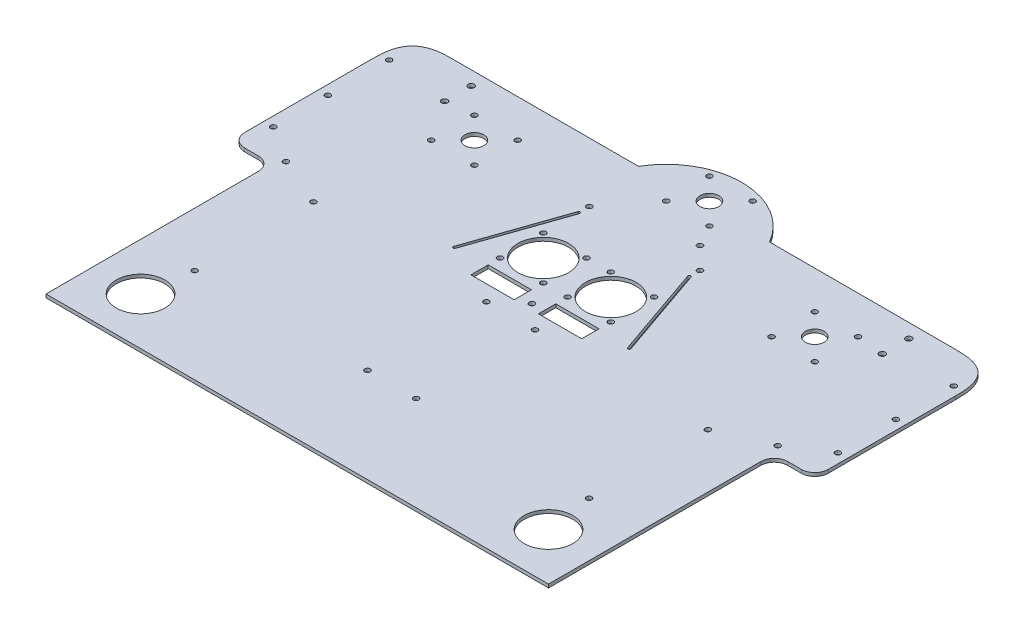
SolidWorks part; units mm, degrees
ref_plane "Front Plane" through (0, 0, 0) normal (0, 0, 1) x (1, 0, 0)
ref_plane "Top Plane" through (0, 0, 0) normal (0, 1, 0) x (1, 0, 0)
ref_plane "Right Plane" through (0, 0, 0) normal (1, 0, 0) x (0, 0, -1)
sketch "Sketch1" plane through (0, 0, 0) normal (0, 1, 0) x (1, 0, 0)
  line L1 (-103.134, 171.9149) -> (328.866, 171.9149)
  line L2 (-103.134, 171.9149) -> (-103.134, -28.0851)
  line L3 (-103.134, -28.0851) -> (328.866, -28.0851)
  line L4 (328.866, 171.9149) -> (328.866, -28.0851)
extrude "Boss-Extrude1" add sketch "Sketch1" along normal blind 2.5 contours L1 L4 L3 L2
sketch "Sketch3" plane through (0, 2.5, 0) normal (0, 1, 0) x (1, 0, 0)
  line L0 (-13.134, 71.9149) -> (-29.1359, 55.9131)
  line L1 (2.8678, 87.9167) -> (-29.1359, 87.9167)
  line L2 (2.8678, 87.9167) -> (2.8678, 55.9131)
  line L3 (2.8678, 55.9131) -> (-29.1359, 55.9131)
  line L4 (-29.1359, 87.9167) -> (-29.1359, 55.9131)
  line L5 (2.8678, 87.9167) -> (-29.1359, 55.9131) construction
  line L6 (2.8678, 55.9131) -> (-29.1359, 87.9167) construction
  line L7 (-103.134, 71.9149) -> (-13.134, 71.9149)
  line L8 (-103.134, 171.9149) -> (-103.134, -28.0851) construction
  line L9 (238.866, 71.9149) -> (238.866, 115.9149)
  line L14 (62.253, -0.3819) -> (46.2512, -16.3837)
  line L15 (238.866, 115.9149) -> (328.866, 115.9149)
  line L18 (328.866, 171.9149) -> (328.866, -28.0851) construction
  line L19 (238.866, 71.9149) -> (222.8641, 55.9131)
  line L20 (254.8678, 87.9167) -> (222.8641, 87.9167)
  line L21 (254.8678, 87.9167) -> (254.8678, 55.9131)
  line L22 (254.8678, 55.9131) -> (222.8641, 55.9131)
  line L23 (222.8641, 87.9167) -> (222.8641, 55.9131)
  line L24 (254.8678, 87.9167) -> (222.8641, 55.9131) construction
  line L25 (254.8678, 55.9131) -> (222.8641, 87.9167) construction
  line L27 (328.866, 71.9149) -> (238.866, 71.9149)
  line L28 (238.866, 115.9149) -> (238.866, 171.9149)
  line L29 (238.866, 171.9149) -> (328.866, 171.9149)
  line L30 (328.866, 115.9149) -> (328.866, 171.9149)
  line L31 (328.866, 115.9149) -> (-169.3435, 115.9149)
  line L32 (328.866, 115.9149) -> (328.866, 173.2785)
  line L33 (328.866, 173.2785) -> (-169.3435, 173.2785)
  line L34 (-169.3435, 115.9149) -> (-169.3435, 173.2785)
  line L35 (78.2549, 15.6199) -> (46.2512, 15.6199)
  line L36 (78.2549, 15.6199) -> (78.2549, -16.3837)
  line L37 (78.2549, -16.3837) -> (46.2512, -16.3837)
  line L38 (46.2512, 15.6199) -> (46.2512, -16.3837)
  line L39 (78.2549, 15.6199) -> (46.2512, -16.3837) construction
  line L40 (78.2549, -16.3837) -> (46.2512, 15.6199) construction
  circle A0 centre (-13.134, 71.9149) radius 7
  circle A1 centre (-29.1359, 55.9131) radius 2
  circle A2 centre (-29.1359, 87.9167) radius 2
  circle A3 centre (2.8678, 87.9167) radius 2
  circle A4 centre (2.8678, 55.9131) radius 2
  circle A10 centre (238.866, 71.9149) radius 7
  circle A11 centre (222.8641, 55.9131) radius 2
  circle A12 centre (222.8641, 87.9167) radius 2
  circle A13 centre (254.8678, 87.9167) radius 2
  circle A14 centre (254.8678, 55.9131) radius 2
  circle A15 centre (62.253, -0.3819) radius 7
  circle A16 centre (46.2512, -16.3837) radius 2
  circle A17 centre (46.2512, 15.6199) radius 2
  circle A18 centre (78.2549, 15.6199) radius 2
  circle A19 centre (78.2549, -16.3837) radius 2
  point P10 (328.866, 71.9149)
extrude "Cut-Extrude1" cut sketch "Sketch3" against normal blind 2.5 contours A2 | A3 | A4 | A1 | A0 | A11 | A14 | A13 | A10 | A12 | L32 L31 L34 L33
sketch "Sketch5" plane through (0, 2.5, 0) normal (0, 1, 0) x (1, 0, 0)
  line L0 (263.7413, -28.0851) -> (263.7413, -18.0851)
  line L3 (-103.134, -28.0851) -> (328.866, -28.0851) construction
  line L5 (263.7413, -18.0851) -> (328.866, -18.0851)
  line L6 (263.7413, -18.0851) -> (263.7413, -28.0851)
  line L7 (263.7413, -28.0851) -> (328.866, -28.0851)
  line L8 (328.866, -18.0851) -> (328.866, -28.0851)
  line L9 (263.7413, -18.0851) -> (-103.134, -18.0851)
  line L10 (263.7413, -18.0851) -> (263.7413, -28.0851)
  line L11 (263.7413, -28.0851) -> (-103.134, -28.0851)
  line L12 (-103.134, -18.0851) -> (-103.134, -28.0851)
  line M12 (328.866, -28.0851) -> (328.866, 115.9149)
  line M14 (-103.134, 115.9149) -> (-103.134, -28.0851)
  line M15 (-103.134, -28.0851) -> (328.866, -28.0851)
extrude "Cut-Extrude3" cut sketch "Sketch5" against normal blind 2.5 contours L0 L9 M14 M15 | L5 L0 M15 M12 region at (80.3036, 2.5, 23.0851) region at (296.3036, 2.5, 23.0851)
sketch "Sketch6" plane through (0, 2.5, 0) normal (0, 1, 0) x (1, 0, 0)
  line L0 (328.866, -18.0851) -> (-103.134, -18.0851) construction
  line L1 (112.866, -18.0851) -> (112.866, 21.9149)
  line L2 (112.866, 21.9149) -> (137.866, 21.9149)
  line L3 (112.866, 21.9149) -> (87.866, 21.9149)
  line L4 (87.866, 21.9149) -> (71.8641, 5.9131)
  line L5 (103.8678, 37.9167) -> (71.8641, 37.9167)
  line L6 (103.8678, 37.9167) -> (103.8678, 5.9131)
  line L7 (103.8678, 5.9131) -> (71.8641, 5.9131)
  line L8 (71.8641, 37.9167) -> (71.8641, 5.9131)
  line L9 (103.8678, 37.9167) -> (71.8641, 5.9131) construction
  line L10 (103.8678, 5.9131) -> (71.8641, 37.9167) construction
  line L11 (137.866, 21.9149) -> (121.8641, 5.9131)
  line L12 (153.8678, 37.9167) -> (121.8641, 37.9167)
  line L13 (153.8678, 37.9167) -> (153.8678, 5.9131)
  line L14 (153.8678, 5.9131) -> (121.8641, 5.9131)
  line L15 (121.8641, 37.9167) -> (121.8641, 5.9131)
  line L16 (153.8678, 37.9167) -> (121.8641, 5.9131) construction
  line L17 (153.8678, 5.9131) -> (121.8641, 37.9167) construction
  circle A0 centre (137.866, 21.9149) radius 18.75
  circle A1 centre (87.866, 21.9149) radius 18.75
  circle A2 centre (87.866, 21.9149) radius 7
  circle A3 centre (71.8641, 5.9131) radius 2
  circle A4 centre (71.8641, 37.9167) radius 2
  circle A5 centre (103.8678, 37.9167) radius 2
  circle A6 centre (103.8678, 5.9131) radius 2
  circle A7 centre (137.866, 21.9149) radius 7
  circle A8 centre (121.8641, 5.9131) radius 2
  circle A9 centre (121.8641, 37.9167) radius 2
  circle A10 centre (153.8678, 37.9167) radius 2
  circle A11 centre (153.8678, 5.9131) radius 2
  point P0 (112.866, -18.0851)
extrude "Cut-Extrude4" cut sketch "Sketch6" against normal blind 2.5 contours A11 | A8 | A10 | A9 | A5 | A6 | A3 | A4
sketch "Sketch8" plane through (0, 2.5, 0) normal (0, 1, 0) x (1, 0, 0)
  line L2 (153.8678, 5.9131) -> (153.8678, 90.0973)
  line L3 (153.8678, 90.0973) -> (71.8641, 90.0973)
  line L4 (71.8641, 90.0973) -> (71.8641, 5.9131)
  line L5 (153.8678, 64.0929) -> (71.8641, 64.0929)
  line L10 (177.527, -4.0851) -> (153.8678, 64.0929) construction
  line L14 (176.5823, -4.4129) -> (152.9231, 63.7651)
  line L15 (178.4718, -3.7572) -> (154.8125, 64.4208)
  line L16 (48.2049, -4.0851) -> (71.8641, 64.0929) construction
  line L17 (47.2602, -3.7572) -> (70.9194, 64.4208)
  line L18 (49.1496, -4.4129) -> (72.8089, 63.7651)
  arc A6 (176.5823, -4.4129) -> (178.4718, -3.7572) centre (177.527, -4.0851) ccw
  arc A7 (154.8125, 64.4208) -> (152.9231, 63.7651) centre (153.8678, 64.0929) ccw
  arc A8 (47.2602, -3.7572) -> (49.1496, -4.4129) centre (48.2049, -4.0851) ccw
  arc A9 (72.8089, 63.7651) -> (70.9194, 64.4208) centre (71.8641, 64.0929) ccw
  point P17 (177.527, 5.9131)
  point P18 (48.2049, 5.9131)
  point P19 (165.6974, 30.0039)
  point P22 (112.866, -4.0851)
  point P27 (60.0345, 30.0039)
extrude "Cut-Extrude5" cut sketch "Sketch8" against normal blind 2.5 contours L17 A9 L18 A8 | L15 A7 L14 A6
fillet "Fillet1" radius 30 2 edges at (-103.134, 1.25, -115.9149) (328.866, 1.25, -115.9149) curvature continuous yes
sketch "Sketch9" plane through (0, 2.5, 0) normal (0, 1, 0) x (1, 0, 0)
  line L0 (328.866, 62.6221) -> (321.866, 62.6221)
  line L1 (328.866, 85.9149) -> (328.866, -18.0851) construction
  line L2 (321.866, 109.7214) -> (321.866, -11.8915)
  line L3 (321.866, 6.0103) -> (321.866, -11.8915)
  line L4 (321.866, 109.7214) -> (321.866, 91.8196)
  line L5 (321.866, 91.8196) -> (321.866, 109.7214)
  line L6 (-103.134, 46.4673) -> (-96.134, 46.4673)
  line L7 (-103.134, 85.9149) -> (-103.134, -18.0851) construction
  line L8 (-96.134, 46.4673) -> (-96.134, 109.7214)
  line L9 (-96.134, 109.7214) -> (-96.134, -11.8916)
  line L10 (-96.134, -11.8916) -> (-96.134, 6.0103)
  line L11 (-96.134, 109.7214) -> (-96.134, 97.3154)
  line L12 (-96.134, 109.7214) -> (-96.134, 91.8196)
  circle A0 centre (321.866, 6.0103) radius 2
  circle A1 centre (321.866, 48.9149) radius 2
  circle A2 centre (321.866, 91.8196) radius 2
  circle A3 centre (-96.134, 46.4673) radius 2
  circle A4 centre (-96.134, 91.8196) radius 2
  circle A5 centre (-96.134, 6.0103) radius 2
  spline S0 degree 2 poles (328.866, 85.9149) (328.866, 87.9765) (328.8467, 89.0459) (328.8162, 90.7467) (328.7231, 92.1742) (328.5043, 95.5283) (327.8783, 98.3317) (326.3274, 105.2776) (322.2688, 109.3319) (318.2198, 113.3765) (311.2895, 114.9258) (308.4764, 115.5546) (305.1048, 115.7733) (303.6844, 115.8655) (301.9893, 115.8958) (300.9233, 115.9149) (298.866, 115.9149) knots 0 0 0 0.0625 0.0625 0.125 0.125 0.25 0.25 0.5 0.5 0.75 0.75 0.875 0.875 0.9375 0.9375 1 1 1 construction
  spline S1 degree 2 poles (298.866, -18.0851) (300.9275, -18.0851) (301.997, -18.0659) (303.6978, -18.0353) (305.1253, -17.9422) (308.4794, -17.7234) (311.2827, -17.0975) (318.2287, -15.5466) (322.283, -11.4879) (326.3276, -7.4389) (327.8768, -0.5086) (328.5057, 2.3045) (328.7244, 5.6761) (328.8165, 7.0965) (328.8469, 8.7916) (328.866, 9.8575) (328.866, 11.9149) knots 0 0 0 0.0625 0.0625 0.125 0.125 0.25 0.25 0.5 0.5 0.75 0.75 0.875 0.875 0.9375 0.9375 1 1 1 construction
  spline S2 degree 2 poles (-73.134, 115.9149) (-75.1956, 115.9149) (-76.2651, 115.8957) (-77.9658, 115.8651) (-79.3933, 115.772) (-82.7474, 115.5532) (-85.5508, 114.9273) (-92.4967, 113.3764) (-96.551, 109.3177) (-100.5957, 105.2687) (-102.1449, 98.3384) (-102.7737, 95.5254) (-102.9924, 92.1538) (-103.0846, 90.7333) (-103.1149, 89.0383) (-103.134, 87.9723) (-103.134, 85.9149) knots 0 0 0 0.0625 0.0625 0.125 0.125 0.25 0.25 0.5 0.5 0.75 0.75 0.875 0.875 0.9375 0.9375 1 1 1 construction
  spline S3 degree 2 poles (-103.134, 11.9149) (-103.134, 9.8534) (-103.1148, 8.7839) (-103.0842, 7.0831) (-102.9911, 5.6556) (-102.7723, 2.3015) (-102.1464, -0.5019) (-100.5955, -7.4478) (-96.5368, -11.5021) (-92.4879, -15.5467) (-85.5575, -17.0959) (-82.7445, -17.7248) (-79.3729, -17.9435) (-77.9525, -18.0356) (-76.2574, -18.066) (-75.1914, -18.0851) (-73.134, -18.0851) knots 0 0 0 0.0625 0.0625 0.125 0.125 0.25 0.25 0.5 0.5 0.75 0.75 0.875 0.875 0.9375 0.9375 1 1 1 construction
extrude "Cut-Extrude6" cut sketch "Sketch9" against normal blind 2.5 contours A0 | A1 | A2 | A5 | A3 | A4
sketch "Sketch10" plane through (0, 2.5, 0) normal (0, 1, 0) x (1, 0, 0)
  line L0 (232.1904, -18.0851) -> (232.1904, -11.5851)
  line L1 (328.866, -18.0851) -> (-103.134, -18.0851) construction
  line L2 (322.1851, -11.5851) -> (-96.4532, -11.5851)
  line L3 (322.1851, -11.5851) -> (232.1904, -11.5851)
  line L4 (322.1851, -11.5851) -> (232.1904, -11.5851)
  line L5 (322.1851, -11.5851) -> (232.1904, -11.5851)
  line L6 (322.1851, -11.5851) -> (294.9418, -11.5851)
  line L7 (-96.4532, -11.5851) -> (-78.7572, -11.5851)
  line L8 (-96.4532, -11.5851) -> (-69.2097, -11.5851)
  circle A0 centre (112.866, -11.5851) radius 2
  circle A3 centre (294.9418, -11.5851) radius 2
  circle A4 centre (-69.2097, -11.5851) radius 2
  spline S0 degree 2 poles (298.866, -18.0851) (300.9275, -18.0851) (301.997, -18.0659) (303.6978, -18.0353) (305.1253, -17.9422) (308.4794, -17.7234) (311.2827, -17.0975) (318.2287, -15.5466) (322.283, -11.4879) (326.3276, -7.4389) (327.8768, -0.5086) (328.5057, 2.3045) (328.7244, 5.6761) (328.8165, 7.0965) (328.8469, 8.7916) (328.866, 9.8575) (328.866, 11.9149) knots 0 0 0 0.0625 0.0625 0.125 0.125 0.25 0.25 0.5 0.5 0.75 0.75 0.875 0.875 0.9375 0.9375 1 1 1 construction
  spline S1 degree 2 poles (-103.134, 11.9149) (-103.134, 9.8534) (-103.1148, 8.7839) (-103.0842, 7.0831) (-102.9911, 5.6556) (-102.7723, 2.3015) (-102.1464, -0.5019) (-100.5955, -7.4478) (-96.5368, -11.5021) (-92.4879, -15.5467) (-85.5575, -17.0959) (-82.7445, -17.7248) (-79.3729, -17.9435) (-77.9525, -18.0356) (-76.2574, -18.066) (-75.1914, -18.0851) (-73.134, -18.0851) knots 0 0 0 0.0625 0.0625 0.125 0.125 0.25 0.25 0.5 0.5 0.75 0.75 0.875 0.875 0.9375 0.9375 1 1 1 construction
extrude "Cut-Extrude7" cut sketch "Sketch10" against normal blind 2.5 contours A4 | A0 | A3
extrude "Cut-Extrude8" cut sketch "Sketch6<3>" against normal blind 10 contours A1 | A0
sketch "Sketch6<3>" plane through (0, 2.5, 0) normal (0, 1, 0) x (1, 0, 0) same geometry as "Sketch6"
sketch "Sketch12" plane through (0, 2.5, 0) normal (0, 1, 0) x (1, 0, 0)
  line L0 (121.8641, 37.9167) -> (121.8641, 71.9149)
  line L1 (238.866, 71.9149) -> (-13.134, 71.9149)
  line L3 (121.8641, 71.9149) -> (105.8623, 55.9131)
  line L4 (137.866, 87.9167) -> (105.8623, 87.9167)
  line L5 (137.866, 87.9167) -> (137.866, 55.9131)
  line L6 (137.866, 55.9131) -> (105.8623, 55.9131)
  line L7 (105.8623, 87.9167) -> (105.8623, 55.9131)
  line L8 (137.866, 87.9167) -> (105.8623, 55.9131) construction
  line L9 (137.866, 55.9131) -> (105.8623, 87.9167) construction
  circle A1 centre (121.8641, 71.9149) radius 7
  circle A2 centre (105.8623, 55.9131) radius 2
  circle A3 centre (105.8623, 87.9167) radius 2
  circle A4 centre (137.866, 87.9167) radius 2
  circle A5 centre (137.866, 55.9131) radius 2
extrude "Cut-Extrude9" cut sketch "Sketch12" against normal blind 10 contours A4
sketch "Sketch13" plane through (0, 2.5, 0) normal (0, 1, 0) x (1, 0, 0)
  line L0 (328.866, 85.9149) -> (274.866, 85.9149)
  line L1 (274.866, 85.9149) -> (274.866, 105.5149)
  line L2 (-103.134, 85.9149) -> (-49.134, 85.9149)
  line L3 (-49.134, 85.9149) -> (-49.134, 105.5149)
  circle A0 centre (274.866, 85.9149) radius 2.25
  circle A1 centre (274.866, 105.5149) radius 2.25
  circle A2 centre (-49.134, 85.9149) radius 2.25
  circle A3 centre (-49.134, 105.5149) radius 2.25
extrude "Cut-Extrude10" cut sketch "Sketch13" against normal blind 10 contours A0 | A1 | A2 | A3
sketch "Sketch14" plane through (0, 2.5, 0) normal (0, 1, 0) x (1, 0, 0)
  line L0 (153.8678, 37.9167) -> (121.8641, 71.9149)
  line L1 (121.8641, 71.9149) -> (153.8678, 71.9149)
  line L2 (71.8641, 37.9167) -> (71.8641, 71.9149)
  circle A0 centre (153.8678, 71.9149) radius 2
  circle A1 centre (71.8641, 71.9149) radius 2
extrude "Cut-Extrude12" cut sketch "Sketch14" against normal blind 2.5 contours A0 | A1
sketch "Sketch19" plane through (0, 2.5, 0) normal (0, 1, 0) x (1, 0, 0)
  line L0 (-73.134, -18.0851) -> (298.866, -18.0851)
  line L1 (-73.134, -18.0851) -> (-73.134, -185.2034)
  line L2 (298.866, -18.0851) -> (298.866, -185.2034)
  line L3 (-73.134, -185.2034) -> (298.866, -185.2034)
extrude "Boss-Extrude5" add sketch "Sketch19" against normal blind 2.5
fillet "Fillet3" radius 10 4 edges at (-103.134, 1.25, 18.0851) (-73.134, 1.25, 18.0851) (328.866, 1.25, 18.0851) (298.866, 1.25, 18.0851)
sketch "Sketch21" plane through (0, 2.5, 0) normal (0, 1, 0) x (1, 0, 0)
  line L1 (298.866, -185.2034) -> (258.866, -185.2034)
  line L2 (298.866, -185.2034) -> (298.866, -115.2034)
  line L3 (298.866, -115.2034) -> (258.866, -115.2034)
  line L4 (258.866, -185.2034) -> (258.866, -115.2034)
  line L5 (258.866, -115.2034) -> (130.866, -115.2034)
  line L6 (258.866, -115.2034) -> (258.866, -27.2034)
  line L7 (258.866, -27.2034) -> (130.866, -27.2034)
  line L8 (130.866, -115.2034) -> (130.866, -27.2034)
  line L9 (-73.134, -185.2034) -> (-33.134, -185.2034)
  line L10 (-73.134, -185.2034) -> (-73.134, -115.2034)
  line L11 (-73.134, -115.2034) -> (-33.134, -115.2034)
  line L12 (-33.134, -185.2034) -> (-33.134, -115.2034)
  line L13 (-33.134, -115.2034) -> (94.866, -115.2034)
  line L14 (-33.134, -115.2034) -> (-33.134, -27.2034)
  line L15 (-33.134, -27.2034) -> (94.866, -27.2034)
  line L16 (94.866, -115.2034) -> (94.866, -27.2034)
  circle A0 centre (258.866, -115.2034) radius 2
  circle A1 centre (130.866, -115.2034) radius 2
  circle A2 centre (94.866, -115.2034) radius 2
  circle A3 centre (-33.134, -115.2034) radius 2
  circle A4 centre (-33.134, -27.2034) radius 2
  circle A5 centre (94.866, -27.2034) radius 2
  circle A6 centre (258.866, -27.2034) radius 2
  circle A7 centre (130.866, -27.2034) radius 2
extrude "Cut-Extrude14" cut sketch "Sketch21" against normal blind 2.5 contours A0 | A6 | A7 | A5 | A1 | A2 | A4 | A3
sketch "Sketch22" plane through (0, 2.5, 0) normal (0, 1, 0) x (1, 0, 0)
  line L0 (121.8641, 5.9131) -> (121.8641, -11.5851)
  line L1 (153.8678, 5.9131) -> (153.8678, -11.5851)
  line L2 (103.8678, 5.9131) -> (103.8678, -20.5636)
  line L3 (153.8678, -2.836) -> (121.8641, -2.836)
  line L4 (153.8678, -2.836) -> (153.8678, -20.5636)
  line L5 (153.8678, -20.5636) -> (121.8641, -20.5636)
  line L6 (121.8641, -2.836) -> (121.8641, -20.5636)
  line L7 (71.8641, 5.9131) -> (71.8641, -20.5636)
  line L8 (121.8641, -20.5636) -> (121.8641, -15.0679)
  line L9 (103.8678, -20.5636) -> (71.8641, -20.5636)
  line L10 (103.8678, -20.5636) -> (103.8678, -2.836)
  line L11 (103.8678, -2.836) -> (71.8641, -2.836)
  line L12 (71.8641, -20.5636) -> (71.8641, -2.836)
  line L13 (121.8641, -20.5636) -> (121.8641, -18.0057)
  line L14 (153.8678, -20.5636) -> (153.8678, -16.8822)
  line L15 (153.8678, -20.5636) -> (153.8678, -15.6536)
  line L16 (153.8678, -15.6536) -> (121.8641, -15.6536)
  line L17 (121.8641, -15.6536) -> (103.8678, -15.6536)
  line L18 (103.8678, -15.6536) -> (71.8641, -15.6536)
extrude "Cut-Extrude15" cut sketch "Sketch22" against normal blind 10 contours L0 L6 L5 L4 L1 L3 | L2 L11 L7 L9 region at (137.866, 2.5, 9.2448) region at (87.866, 2.5, 9.2448)
sketch "Sketch23" plane through (0, 2.5, 0) normal (0, 1, 0) x (1, 0, 0)
  line L1 (-73.134, -185.2034) -> (-38.134, -185.2034)
  line L2 (-73.134, -185.2034) -> (-73.134, -150.2034)
  line L3 (-73.134, -150.2034) -> (-38.134, -150.2034)
  line L4 (-38.134, -185.2034) -> (-38.134, -150.2034)
  circle A0 centre (-38.134, -150.2034) radius 18
extrude "Cut-Extrude16" cut sketch "Sketch23" against normal blind 26 contours L4 A0 L3 | L3 A0 L4 region at (-45.7735, 2.5, 157.8428) region at (-35.5876, 2.5, 147.6569)
sketch "Sketch24" plane through (0, 2.5, 0) normal (0, 1, 0) x (1, 0, 0)
  line L1 (298.866, -185.2034) -> (263.866, -185.2034)
  line L2 (298.866, -185.2034) -> (298.866, -150.2034)
  line L3 (298.866, -150.2034) -> (263.866, -150.2034)
  line L4 (263.866, -185.2034) -> (263.866, -150.2034)
  circle A0 centre (263.866, -150.2034) radius 18
extrude "Cut-Extrude17" cut sketch "Sketch24" against normal blind 26 contours L3 A0 L4 | L4 A0 L3 region at (261.3195, 2.5, 147.6569) region at (271.5054, 2.5, 157.8428)
sketch "Sketch26" plane through (0, 2.5, 0) normal (0, 1, 0) x (1, 0, 0)
  line L0 (112.866, -11.5851) -> (112.866, 115.9149)
  line L1 (298.866, 115.9149) -> (-73.134, 115.9149) construction
  line L2 (112.866, 115.9149) -> (112.866, 119.8149)
  line L3 (161.3644, 115.9149) -> (64.3675, 115.9149)
  arc A0 (64.3675, 115.9149) -> (161.3644, 115.9149) centre (112.866, 87.9167) cw
extrude "Boss-Extrude6" add sketch "Sketch26" against normal blind 2.5 contours A0 L3
sketch "Sketch27" plane through (0, 2.5, 0) normal (0, 1, 0) x (1, 0, 0)
  line L0 (161.3644, 115.9149) -> (64.3675, 115.9149)
  line L1 (112.866, 115.9149) -> (112.866, 119.8149)
  line L2 (112.866, 119.8149) -> (112.866, 119.92)
  line L3 (298.6293, -177.6896) -> (282.6274, -193.6915)
  line L4 (314.6311, -161.6878) -> (282.6274, -161.6878)
  line L5 (314.6311, -161.6878) -> (314.6311, -193.6915)
  line L6 (314.6311, -193.6915) -> (282.6274, -193.6915)
  line L7 (282.6274, -161.6878) -> (282.6274, -193.6915)
  line L8 (314.6311, -161.6878) -> (282.6274, -193.6915) construction
  line L9 (314.6311, -193.6915) -> (282.6274, -161.6878) construction
  line L10 (112.866, 119.92) -> (96.8641, 103.9182)
  line L11 (128.8678, 135.9219) -> (96.8641, 135.9219)
  line L12 (128.8678, 135.9219) -> (128.8678, 103.9182)
  line L13 (128.8678, 103.9182) -> (96.8641, 103.9182)
  line L14 (96.8641, 135.9219) -> (96.8641, 103.9182)
  line L15 (128.8678, 135.9219) -> (96.8641, 103.9182) construction
  line L16 (128.8678, 103.9182) -> (96.8641, 135.9219) construction
  arc A0 (161.3644, 115.9149) -> (64.3675, 115.9149) centre (112.866, 87.9167) ccw construction
  circle A1 centre (298.6293, -177.6896) radius 18.75
  circle A2 centre (298.6293, -177.6896) radius 7
  circle A3 centre (282.6274, -193.6915) radius 2
  circle A4 centre (282.6274, -161.6878) radius 2
  circle A5 centre (314.6311, -161.6878) radius 2
  circle A6 centre (314.6311, -193.6915) radius 2
  circle A7 centre (112.866, 119.92) radius 18.75
  circle A8 centre (112.866, 119.92) radius 7
  circle A9 centre (96.8641, 103.9182) radius 2
  circle A10 centre (96.8641, 135.9219) radius 2
  circle A11 centre (128.8678, 135.9219) radius 2
  circle A12 centre (128.8678, 103.9182) radius 2
  point P31 (161.3644, -52.7322)
  point P32 (109.4598, 125.4429)
  point P33 (112.866, 120.3732)
extrude "Cut-Extrude18" cut sketch "Sketch27" against normal blind 2.5 contours A11 | A12 | A8 | A9 | A10
